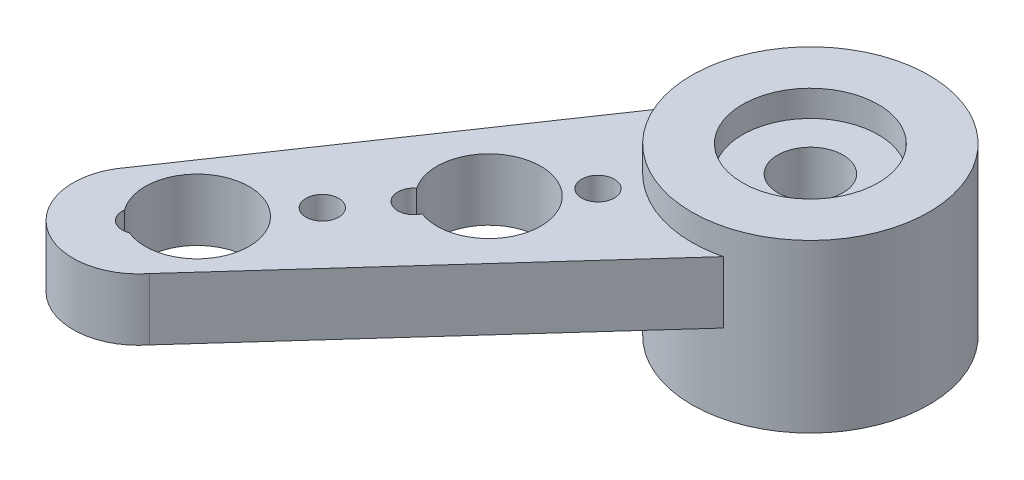
SolidWorks part; units mm, degrees
ref_plane "Front Plane" through (0, 0, 0) normal (0, 0, 1) x (1, 0, 0)
ref_plane "Top Plane" through (0, 0, 0) normal (0, 1, 0) x (1, 0, 0)
ref_plane "Right Plane" through (0, 0, 0) normal (1, 0, 0) x (0, 0, -1)
sketch "Sketch1" plane through (0, 0, 0) normal (0, 1, 0) x (1, 0, 0)
  circle A0 centre (0, 0) radius 3.625
  circle A1 centre (0, 0) radius 2.075
extrude "Boss-Extrude1" add sketch "Sketch1" along normal blind 2.41
sketch "Sketch2" plane through (0, 2.41, 0) normal (0, 1, 0) x (1, 0, 0)
  line L4 (-10.6055, -10.2672) -> (-3.625, 0)
  line L5 (-7.4595, -12.7376) -> (0.8596, -3.5216)
  circle A0 centre (0, 0) radius 1
  arc A1 (0.8596, -3.5216) -> (-3.625, 0) centre (0, 0) ccw
  arc A2 (-10.6055, -10.2672) -> (-7.4595, -12.7376) centre (-9.0325, -11.5024) ccw
  circle A4 centre (-9.0325, -11.5024) radius 0.5
  circle A5 centre (-7.7973, -9.9294) radius 0.5
  circle A6 centre (-6.5621, -8.3564) radius 0.5
  circle A7 centre (-5.3268, -6.7835) radius 0.5
  circle A8 centre (-4.0916, -5.2105) radius 0.5
  circle A9 centre (-2.8564, -3.6375) radius 0.5
  point P7 (-2.2388, -2.851)
extrude "Boss-Extrude3" add sketch "Sketch2" along normal blind 1.89
extrude "Boss-Extrude4" add sketch "Sketch1<2>" along normal blind 0.8 from surface starting at face at (-4.0916, 4.3, 5.7105)
sketch "Sketch1<2>" plane through (0, 0, 0) normal (0, 1, 0) x (1, 0, 0) same geometry as "Sketch1"
sketch "Sketch3" plane through (0, 4.3, 0) normal (0, 1, 0) x (1, 0, 0)
  line L0 (0, 0) -> (-9.0325, -11.5024) construction
  circle A0 centre (-8.245, -10.4996) radius 1.5875
  circle A1 centre (-4.3232, -5.5054) radius 1.5875
  circle A2 centre (-9.0325, -11.5024) radius 0.5 construction
  point P4 (0, 0)
  point P5 (0, 0)
  point P8 (0, 0)
  point P9 (0, 0)
  point P10 (-8.9264, -11.6165)
  point P14 (0, 0)
  dimension "D1" = 3.175
  dimension "D2" = 6.35
  dimension "D3" = 7
extrude "Cut-Extrude1" cut sketch "Sketch3" against normal through all
